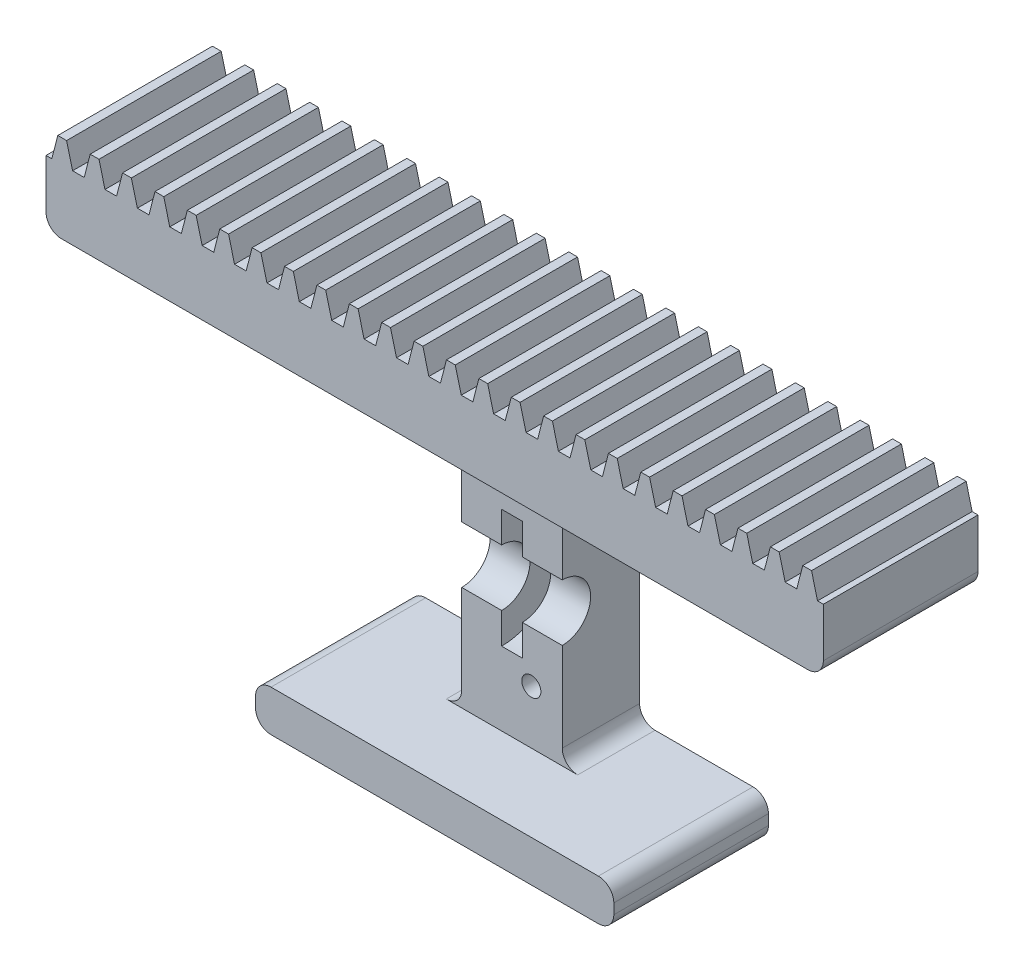
SolidWorks part; units mm, degrees
extrude "Blank Cremalheira" add sketch "BlankSke" against normal blind 30
sketch "BlankSke" plane through (0, 0, 0) normal (0, 0, 1) x (1, 0, 0)
  line L1 (0, 0) -> (150.8, 0)
  line L2 (0, 0) -> (0, 17)
  line L3 (0, 17) -> (150.8, 17)
  line L4 (150.8, 0) -> (150.8, 17)
  dimension "Length" = 150.8
ref_plane "Plane1" through (0, 0, 0) normal (0, 0, 1) x (1, 0, 0)
ref_plane "Plane2" through (0, 0, 0) normal (0, 1, 0) x (1, 0, 0)
ref_plane "Plane3" through (0, 0, 0) normal (1, 0, 0) x (0, 0, -1)
sketch "HoldingSke" plane through (0, 0, 0) normal (0, 1, 0) x (1, 0, 0)
  line L0 (0, 0) -> (0.0696, 0.4951)
  line L1 (-15, 0) -> (100, 0) construction
  line L2 (0, 0) -> (-2.1039, 2.3779)
  line L3 (0, 0) -> (-11.863, 4.5341)
  line L4 (0, 0) -> (7.762, 3.7858)
  line L5 (0, 0) -> (-23.7986, -8.8762)
  line L6 (0, 0) -> (-10.5278, -7.1032)
  line L9 (-67.7845, 28.3722) -> (78.2121, 66.1296)
  line L10 (-76.2, 4.3779) -> (-61.2, 4.3779)
  line L11 (0, 0) -> (-30, 0)
  line L12 (-76.2, 101.6) -> (-76.133, 101.6)
  line L13 (24.9733, 27.94) -> (52.9518, 28.4284)
  line L14 (24.9733, 27.94) -> (24.9743, 27.94)
  line L15 (24.9733, 27.94) -> (100.4006, 29.5858)
  circle A0 centre (0, 0) radius 19.05
  circle A1 centre (0, 0) radius 7.5
  circle A2 centre (0, 0) radius 12.7
  dimension "Num_teeth" = 26
  dimension "Width" = 30
  dimension "Length" = 150.8
  dimension "Pitch_height" = 15
sketch "TooCutSkeIll" plane through (0, 0, 0) normal (0, 0, 1) x (1, 0, 0)
  line L0 (-2.2735, 16.94) -> (-1.2224, 12.8756)
  line L1 (-0.7373, 12.5) -> (0.7373, 12.5)
  line L2 (1.2224, 12.8756) -> (2.2735, 16.94)
  line L3 (150.8, 17) -> (0, 17) construction
  line L4 (0, 0) -> (0, 64.897) construction
  line L5 (-13.208, 15) -> (12.954, 15) construction
  line L6 (0, 0) -> (150.8, 0) construction
  line L7 (1.7718, 15) -> (1.7718, 48.7463) construction
  line L8 (-1.7718, 15) -> (-1.7718, 48.7463) construction
  line L9 (2.351, 17) -> (2.351, 17.0254)
  line L10 (-2.351, 17) -> (-2.351, 17.0254)
  line L11 (-2.351, 17.0254) -> (2.351, 17.0254)
  arc A0 (0.7373, 12.5) -> (1.2224, 12.8756) centre (0.7373, 13.001) ccw
  arc A1 (-1.2224, 12.8756) -> (-0.7373, 12.5) centre (-0.7373, 13.001) ccw
  arc A2 (2.351, 17) -> (2.2735, 16.94) centre (2.351, 16.92) ccw
  arc A3 (-2.2735, 16.94) -> (-2.351, 17) centre (-2.351, 16.92) ccw
  dimension "Addendum_plus" = 2.0254
  dimension "Pitch_height" = 15
  dimension "Pressure_angle" = 14.5
  dimension "Gap_width" = 3.5436
  dimension "Dedendum" = 2.5
extrude "ToothCutIll" [suppressed] cut sketch "TooCutSkeIll" against normal through all
sketch "TooCutSkeSim" plane through (0, 0, 0) normal (0, 0, 1) x (1, 0, 0)
  line L0 (1.1253, 12.5) -> (-1.1253, 12.5)
  line L1 (2.2956, 17.0254) -> (1.1253, 12.5)
  line L2 (0, 17.4625) -> (0, 53.467) construction
  line L3 (2.2956, 17.0254) -> (-2.2956, 17.0254)
  line L6 (-2.2956, 17.0254) -> (-1.1253, 12.5)
  line L9 (-1.7718, 15) -> (1.7718, 15) construction
  line L10 (0, 0) -> (150.8, 0) construction
  line L11 (1.7718, 15) -> (1.7718, 53.467) construction
  line L12 (-1.7718, 15) -> (-1.7718, 53.467) construction
  dimension "Addendum_plus" = 2.0254
  dimension "Pitch_height" = 15
  dimension "Pressure_angle" = 14.5
  dimension "Gap_width" = 3.5436
  dimension "Dedendum" = 2.5
extrude "Corte - Dente Dimensionado" cut sketch "TooCutSkeSim" against normal through all
pattern_linear "Corte - Destes" count 26 spacing 6.2832 along (1, 0, 0) of "ToothCutIll", "Corte - Dente Dimensionado"
sketch "Sketch1" plane through (0, 0, -30) normal (0, 0, -1) x (-1, 0, 0)
  line L0 (-75.4, 0) -> (-75.4, -63) construction
  line L1 (0, 0) -> (-150.8, 0) construction
  line L2 (-65.65, -55) -> (-40.65, -55)
  line L6 (-65.65, 0) -> (-65.65, -55)
  line L7 (-40.65, -55) -> (-40.65, -63)
  line L8 (-40.65, -63) -> (-110.15, -63)
  line L9 (-85.15, 0) -> (-65.65, 0)
  line L10 (-110.15, -55) -> (-110.15, -63)
  line L11 (-85.15, -55) -> (-110.15, -55)
  line L12 (-85.15, 0) -> (-85.15, -55)
  line L13 (-85.15, -55) -> (-65.65, -55)
  dimension "D1" = 19.5
  dimension "D2" = 55
  dimension "D3" = 8
  dimension "D4" = 25
extrude "Corpo de Apoio" add sketch "Sketch1" against normal blind 30 contours L9 L0 L13 L6 | L0 L9 L12 L13 | L13 L0 L8 L7 L2 | L0 L13 L11 L10 L8 region at (70.525, -27.5, -30) region at (80.275, -27.5, -30) region at (58.025, -59, -30) region at (92.775, -59, -30)
sketch "Sketch2" plane through (0, 0, 0) normal (0, 0, 1) x (1, 0, 0)
  line L0 (85.15, 0) -> (85.15, -55) construction
  line L1 (65.65, 0) -> (85.15, 0)
  line L2 (65.65, 0) -> (65.65, -55)
  line L3 (65.65, -55) -> (85.15, -55)
  line L4 (85.15, 0) -> (85.15, -55)
extrude "Rebaixo" cut sketch "Sketch2" against normal blind 15
ref_plane "Plano de Referência" through (75.4, 0, 0) normal (-1, 0, 0) x (0, 0, 1)
sketch "Sketch3" plane through (75.4, 0, 0) normal (-1, 0, 0) x (0, 0, 1)
  line L0 (-15, 0) -> (-15, -55) construction
  line L1 (-30, 0) -> (0, 0) construction
  circle A0 centre (-15, -29.25) radius 5.5
  circle A1 centre (-15, -29.25) radius 11.5
  dimension "D1" = 29.25
  dimension "D2" = 11
  dimension "D3" = 23
extrude "Encaixe Flange - Ø11 Passante" cut sketch "Sketch3" against normal through all both and the other way through all contours A0 region at (75.4, -29.25, -15)
extrude "Encaixe Flange - Ø23x4" cut sketch "Sketch3<3>" against normal mid plane 4
sketch "Sketch3<3>" plane through (75.4, 0, 0) normal (-1, 0, 0) x (0, 0, 1) same geometry as "Sketch3"
sketch "Sketch4" plane through (0, 0, -30) normal (0, 0, -1) x (-1, 0, 0)
  line L0 (0, 0) -> (-65.65, 0) construction
  line L1 (-71.65, -3.8431) -> (-75.25, -5.9215)
  line L2 (-75.25, -5.9215) -> (-75.25, -10.0785)
  line L3 (-75.25, -10.0785) -> (-71.65, -12.1569)
  line L4 (-71.65, -12.1569) -> (-68.05, -10.0785)
  line L5 (-68.05, -10.0785) -> (-68.05, -5.9215)
  line L6 (-68.05, -5.9215) -> (-71.65, -3.8431)
  line L7 (-79.15, -40.4431) -> (-82.75, -42.5215)
  line L8 (-82.75, -42.5215) -> (-82.75, -46.6785)
  line L9 (-82.75, -46.6785) -> (-79.15, -48.7569)
  line L10 (-79.15, -48.7569) -> (-75.55, -46.6785)
  line L11 (-75.55, -46.6785) -> (-75.55, -42.5215)
  line L12 (-75.55, -42.5215) -> (-79.15, -40.4431)
  line L13 (-65.65, 0) -> (-65.65, -55) construction
  line L14 (-85.15, 0) -> (-85.15, -55) construction
  line L16 (-110.15, -55) -> (-85.15, -55) construction
  circle A0 centre (-71.65, -8) radius 3.6 construction
  circle A1 centre (-79.15, -44.6) radius 3.6 construction
  dimension "D1" = 7.2
  dimension "D2" = 8
  dimension "D3" = 6
  dimension "D4" = 36.6
  dimension "D5" = 6
  dimension "D6" = 6.2431
  dimension "D7" = 3.8431
extrude "Rebaixos das Porcas" cut sketch "Sketch4" against normal blind 4
sketch "Sketch5" plane through (0, 0, -26) normal (0, 0, -1) x (-1, 0, 0)
  line L0 (-82.75, -42.5215) -> (-82.75, -46.6785) construction
  line L1 (-75.55, -46.6785) -> (-75.55, -42.5215) construction
  line L2 (-79.15, -48.7569) -> (-75.55, -46.6785) construction
  line L3 (-68.05, -5.9215) -> (-71.65, -3.8431) construction
  line L4 (-71.65, -12.1569) -> (-68.05, -10.0785) construction
  line L6 (-75.25, -10.0785) -> (-71.65, -12.1569) construction
  circle A0 centre (-79.15, -44.6) radius 3.6 construction
  circle A1 centre (-79.15, -44.6) radius 1.85
  circle A2 centre (-71.65, -8) radius 3.6 construction
  circle A3 centre (-71.65, -8) radius 1.85
  dimension "D1" = 3.7
extrude "Furos de Fixação" cut sketch "Sketch5" against normal through all
fillet "Raios 3mm" radius 3 8 edges at (110.15, -63, -15) (110.15, -55, -15) (40.65, -63, -15) (65.65, -55, -22.5) (40.65, -55, -15) (85.15, -55, -22.5) (0, 0, -15) (150.8, 0, -15)
fillet "Raios 5mm" radius 5 2 edges at (85.15, 0, -22.5) (65.65, 0, -22.5)
equation "' \"Module@HoldingSke\" = 6.35"
equation "' \"Num_teeth@HoldingSke\" = 12"
equation "' \"Ap@HoldingSke\" =  20"
equation "' \"Ap@HoldingSke\" = 20"
equation "' \"Width@HoldingSke\" = 0.25 * 25.4"
equation "' \"Show_teeth@HoldingSke\" = 500"
equation "' \"Backlash@HoldingSke\" = 0.009 * 25.4"
equation "' \"Addendum_fac@HoldingSke\" = 1.0"
equation "' \"Dedendum_fac@HoldingSke\" = 1.25"
equation "' \"Dedendum_add@HoldingSke\" = 0.00005 * 25.4"
equation "' \"Clearance_fac@HoldingSke\" = 0.25"
equation "' \"Pitch_height@HoldingSke\" = 1 * 25.4"
equation "' \"Length@HoldingSke\" = 4.71 * 25.4"
equation "\"Pitch@HoldingSke\" = 1 / \"Module@HoldingSke\""
equation "\"MPH@HoldingSke\" = \"Dedendum_fac@HoldingSke\" / \"Pitch@HoldingSke\" + 2 * \"Dedendum_add@HoldingSke\" + 0.002 * 25.4"
equation "\"MPH@HoldingSke\" = ((sgn( \"MPH@HoldingSke\" - \"Pitch_height@HoldingSke\")+1)*( \"MPH@HoldingSke\" - \"Pitch_height@HoldingSke\"))/2 + \"Pitch_height@HoldingSke\""
equation "\"Blank_height@BlankSke\" = \"Pitch_height@HoldingSke\" + \"Addendum_fac@HoldingSke\"  / \"Pitch@HoldingSke\" "
equation "\"Length@BlankSke\" =  \"Length@HoldingSke\""
equation "\"Face_width@Blank Cremalheira\" = \"Width@HoldingSke\""
equation "\"Pressure_angle@TooCutSkeIll\" = \"Ap@HoldingSke\""
equation "\"Addendum_plus@TooCutSkeIll\" =  \"Addendum_fac@HoldingSke\"  / \"Pitch@HoldingSke\" + 0.001 *25.4"
equation "\"Dedendum@TooCutSkeIll\" = \"Dedendum_fac@HoldingSke\"  / \"Pitch@HoldingSke\""
equation "\"Pitch_height@TooCutSkeIll\" =  \"MPH@HoldingSke\""
equation "\"Gap_width@TooCutSkeIll\" = 3.14159265 / 2 / \"Pitch@HoldingSke\" + 6 * \"Backlash@HoldingSke\""
equation "\"Pressure_angle@TooCutSkeSim\" = \"Ap@HoldingSke\""
equation "\"Addendum_plus@TooCutSkeSim\" =  \"Addendum_fac@HoldingSke\"  / \"Pitch@HoldingSke\" + 0.001 * 25.4"
equation "\"Dedendum@TooCutSkeSim\" = \"Dedendum_fac@HoldingSke\"  / \"Pitch@HoldingSke\""
equation "\"Pitch_height@TooCutSkeSim\" =  \"MPH@HoldingSke\""
equation "\"Gap_width@TooCutSkeSim\" = 3.14159265 / 2 / \"Pitch@HoldingSke\" + 6 * \"Backlash@HoldingSke\""
equation "\"Root_fillet@TooCutSkeIll\" = \"Clearance_fac@HoldingSke\" / \"Pitch@HoldingSke\" + \"Dedendum_add@HoldingSke\""
equation "\"Break_rad@TooCutSkeIll\" = 0.02 / \"Pitch@HoldingSke\" * 2"
equation "\"Linear_pitch@Corte - Destes\" = 3.14159265 / \"Pitch@HoldingSke\""
equation "\"Num_teeth@HoldingSke\" = int( ( \"Length@HoldingSke\" + 0 ) / (3.14159265 / \"Pitch@HoldingSke\")) + 0.9999  + 1"
equation "\"Num_teeth@Corte - Destes\" = int ( \"Show_teeth@HoldingSke\" )  + 1"
equation "\"Num_teeth@Corte - Destes\" =  (  ( sgn ( \"Num_teeth@Corte - Destes\" - \"Num_teeth@HoldingSke\" )  - 1 )  *  ( \"Num_teeth@Corte - Destes\" - \"Num_teeth@HoldingSke\" )  )  /  - 2 + \"Num_teeth@HoldingSke\""
equation "\"Num_teeth@Corte - Destes\" =  (  ( sgn ( \"Num_teeth@Corte - Destes\" - 2.0 )  + 1 )  *  ( \"Num_teeth@Corte - Destes\" - 2.0 )  )  / 2 + 2.0"
